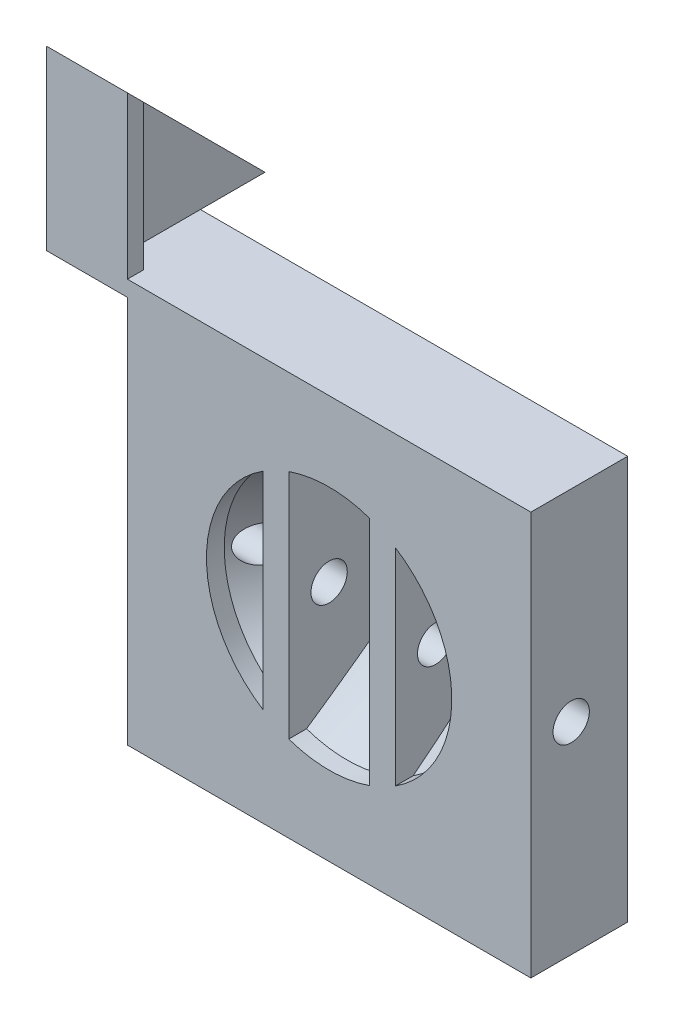
SolidWorks part; units mm, degrees
ref_plane "Alzado" through (0, 0, 0) normal (0, 0, 1) x (1, 0, 0)
ref_plane "Planta" through (0, 0, 0) normal (0, 1, 0) x (1, 0, 0)
ref_plane "Vista lateral" through (0, 0, 0) normal (1, 0, 0) x (0, 0, -1)
sketch "Croquis1" plane through (0, 0, 0) normal (0, 0, 1) x (1, 0, 0)
  line L1 (25, -25) -> (-25, -25)
  line L2 (25, -25) -> (25, 25)
  line L3 (25, 25) -> (-25, 25)
  line L4 (-25, -25) -> (-25, 25)
  line L5 (25, -25) -> (-25, 25) construction
  line L6 (25, 25) -> (-25, -25) construction
  circle A0 centre (0, 0) radius 2
  point P0 (0, 0)
  dimension "D3" = 4
  dimension "D1" = 50
  dimension "D2" = 50
extrude "Saliente-Extruir2" add sketch "Croquis1" along normal blind 12
ref_plane "Plano1" through (0, 0, 0) normal (1, 0, 0) x (0, 0, -1)
sketch "Croquis2" plane through (0, 0, 0) normal (1, 0, 0) x (0, 0, -1)
  line L1 (-12, 25) -> (-12, -25) construction
  line L4 (-12, 15.2) -> (-12, 0)
  line L6 (-9.8, 15.2) -> (-1.8, 10)
  line L7 (-12, 15.2) -> (-9.8, 15.2)
  line L8 (-1.8, 0) -> (-1.8, 10)
  line L9 (-12, 0) -> (-1.8, 0)
  dimension "D1" = 2.2
  dimension "D2" = 10.2
  dimension "D3" = 10
  dimension "D4" = 15.2
revolve "Cortar-Revolución1" cut sketch "Croquis2" angle 360 about L9
sketch "Croquis4" plane through (0, 0, 12) normal (0, 0, 1) x (1, 0, 0)
  line L0 (0, -0.44) -> (0, 0.44) construction
  line L1 (-8.2, 20) -> (-5, 20)
  line L2 (-8.2, 20) -> (-8.2, -20)
  line L3 (-8.2, -20) -> (-5, -20)
  line L4 (-5, 20) -> (-5, -20)
  line L5 (8.2, -20) -> (5, -20)
  line L6 (5, 20) -> (5, -20)
  line L7 (8.2, 20) -> (5, 20)
  line L8 (8.2, 20) -> (8.2, -20)
  point P6 (-5, 0)
  dimension "D1" = 3.2
  dimension "D2" = 5
  dimension "D3" = 40
extrude "Saliente-Extruir5" add sketch "Croquis4" along direction (0, 0, 1) on the side against the normal up to surface (10.2 mm away) up to face at (0, -2, 1.8)
sketch "Croquis7" plane through (-25, 0, 0) normal (-1, 0, 0) x (0, 0, 1)
  line L1 (12, 25) -> (12, -25) construction
  circle A0 centre (7, 0) radius 2
  dimension "D1" = 4
  dimension "D2" = 5
extrude "Cortar-Extruir2" cut sketch "Croquis7" against normal up to vertex (50 mm away) up to point (25, -25, 12)
hole_wizard "Refrentado para tornillo tapón con cabeza plana de clavija de M41" positions "Croquis10" profile "Croquis11" countersink size "M4" standard "Ansi Metric" end condition through all
sketch "Croquis10" plane through (-25, 0, 0) normal (-1, 0, 0) x (0, 0, 1)
  point P0 (7, 0)
sketch "Croquis11" plane through (-25, 0, 7) normal (0, 1, 0) x (0, 0, 1)
  line L0 (0, 0) -> (0, 50)
  line L1 (0, 50) -> (2.25, 50)
  line L2 (2.25, 50) -> (2.25, 2.23)
  line L3 (2.25, 2.23) -> (4.48, 0)
  line L5 (4.48, 0) -> (0, 0)
  line L6 (-2.25, 2.23) -> (-4.48, 0) construction
  line L11 (0, -6.35) -> (0, 107.95) construction
  dimension "Diámetro de taladro hasta el siguiente" = 4.5
  dimension "Profundidad de taladro hasta el siguiente" = 50
  dimension "Diámetro de avellanado cercano" = 8.96
  dimension "Ángulo de avellanado cercano" = 90
hole_wizard "Refrentado para tornillo tapón con cabeza plana de clavija de M42" positions "Croquis16" profile "Croquis17" countersink size "M4" standard "Ansi Metric" end condition through all
sketch "Croquis16" plane through (0, 0, 1.8) normal (0, 0, 1) x (1, 0, 0)
  point P0 (0, 0)
sketch "Croquis17" plane through (0, 0, 1.8) normal (1, 0, 0) x (0, -1, 0)
  line L0 (0, 0) -> (0, 1.8)
  line L1 (0, 1.8) -> (2.25, 1.8)
  line L2 (2.25, 1.8) -> (2.25, 2.23)
  line L3 (2.25, 2.23) -> (4.48, 0)
  line L5 (4.48, 0) -> (0, 0)
  line L6 (-2.25, 2.23) -> (-4.48, 0) construction
  line L11 (0, -6.35) -> (0, 107.95) construction
  dimension "Diámetro de taladro hasta el siguiente" = 4.5
  dimension "Profundidad de taladro hasta el siguiente" = 1.8
  dimension "Diámetro de avellanado cercano" = 8.96
  dimension "Ángulo de avellanado cercano" = 90
sketch "Croquis12" plane through (-25, 0, 0) normal (-1, 0, 0) x (0, 0, 1)
  line L2 (12, 0) -> (0, 0) construction
  line L5 (12, 25) -> (12, -25) construction
  line L6 (0, 25) -> (0, -25) construction
  line L7 (12, 45) -> (-8, 25)
  line L8 (12, 25) -> (12, 45)
  line L9 (12, 25) -> (-8, 25)
  dimension "D1" = 20
  dimension "D2" = 20
sketch "Croquis19" plane through (-25, 0, 0) normal (-1, 0, 0) x (0, 0, 1)
  line L0 (0, 25) -> (0, -25) construction
  line L1 (12, 45) -> (10, 43)
  line L3 (10, 43) -> (10, 25)
  line L4 (0, 25) -> (10, 25)
  line L7 (12, 25) -> (12, 45)
  line L8 (0, 25) -> (0, 23.05)
  line L10 (10, 23.05) -> (0, 23.05)
  line L11 (10, 23.05) -> (12, 23.05)
  line L12 (12, 25) -> (12, -25) construction
  line L13 (12, 23.05) -> (12, 25)
  dimension "D2" = 1.95
  dimension "D3" = 2
extrude "Saliente-Extruir14" add sketch "Croquis19" along normal blind 10.05
extrude "Saliente-Extruir15" add sketch "Croquis12" along normal blind 1.95 from offset 2.95
extrude "Saliente-Extruir16" add sketch "Croquis12<3>" against normal blind 1.95 from surface starting at face at (-35.05, 30.6833, 7.3333)
sketch "Croquis12<3>" plane through (-25, 0, 0) normal (-1, 0, 0) x (0, 0, 1) same geometry as "Croquis12"
